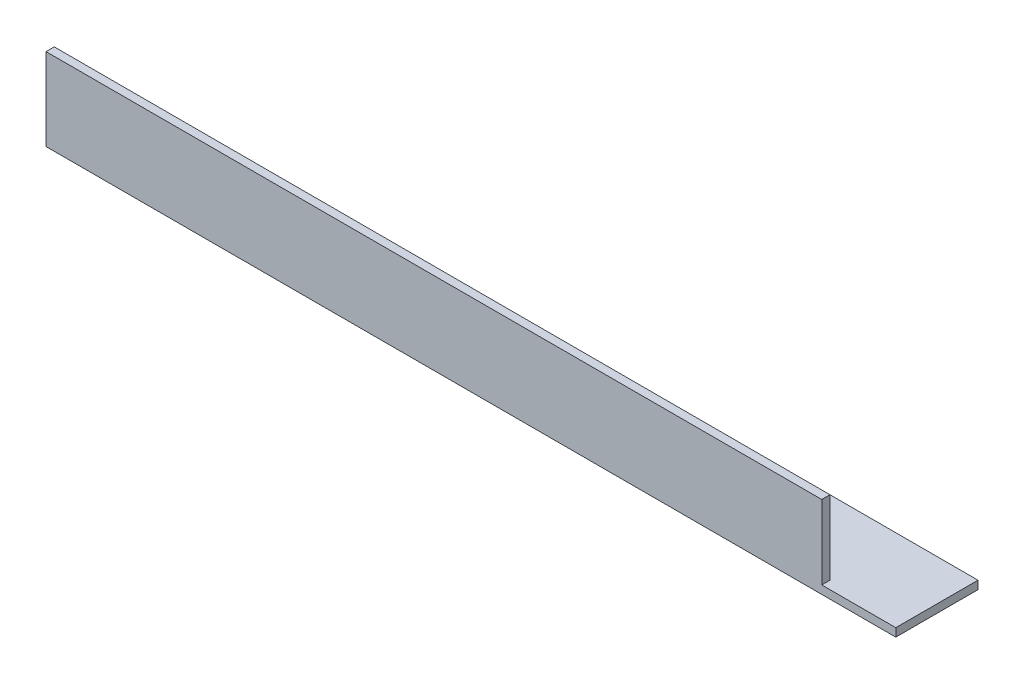
SolidWorks part; units mm, degrees
ref_plane "Спереди" through (0, 0, 0) normal (0, 0, 1) x (1, 0, 0)
ref_plane "Сверху" through (0, 0, 0) normal (0, 1, 0) x (1, 0, 0)
ref_plane "Справа" through (0, 0, 0) normal (1, 0, 0) x (0, 0, -1)
sketch "Эскиз1" plane through (0, 0, 0) normal (1, 0, 0) x (0, 0, -1)
  line L0 (0, 0) -> (30, 0)
  line L1 (0, 0) -> (0, 30)
extrude "Вытянуть-Тонкостенный1" add sketch "Эскиз1" along normal blind 310 thin thin type one direction wall 3
sketch "Эскиз2" plane through (0, 0, 0) normal (0, 0, 1) x (1, 0, 0)
  line L1 (310, 30) -> (283, 30)
  line L2 (310, 30) -> (310, 3)
  line L3 (310, 3) -> (283, 3)
  line L4 (283, 30) -> (283, 3)
extrude "Вырез-Вытянуть1" cut sketch "Эскиз2" against normal through all
